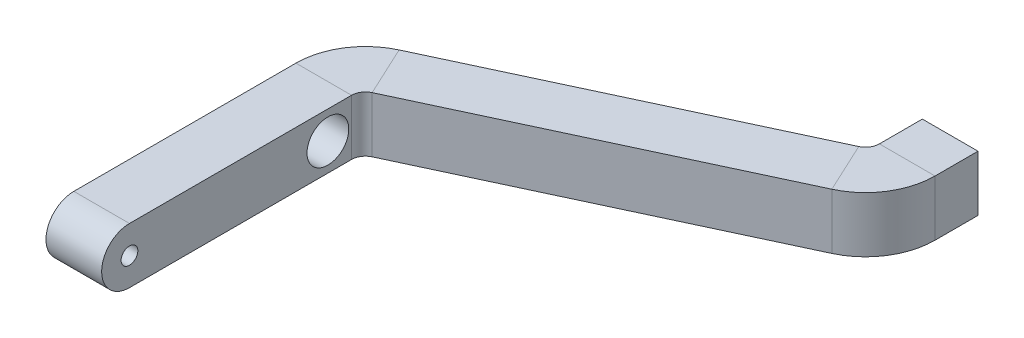
SolidWorks part; units mm, degrees
ref_plane "前视基准面" through (0, 0, 0) normal (0, 0, 1) x (1, 0, 0)
ref_plane "上视基准面" through (0, 0, 0) normal (0, 1, 0) x (1, 0, 0)
ref_plane "右视基准面" through (0, 0, 0) normal (1, 0, 0) x (0, 0, -1)
sketch "草图1" plane through (0, 0, 0) normal (0, 1, 0) x (1, 0, 0)
  line L0 (0, 0) -> (0, -30.8879)
  line L1 (-17.3215, -58.0771) -> (-242.6785, -163.1629)
  line L2 (-260, -190.3521) -> (-260, -370)
  arc A0 (-242.6785, -163.1629) -> (-260, -190.3521) centre (-230, -190.3521) ccw
  arc A1 (0, -30.8879) -> (-17.3215, -58.0771) centre (-30, -30.8879) cw
  point P9 (0, -50)
  dimension "D5" = 30
  dimension "D1" = 260
  dimension "D2" = 115
  dimension "D3" = 370
  dimension "D4" = 50
sketch "草图2" plane through (0, 0, 0) normal (0, 0, 1) x (1, 0, 0)
  line L1 (-20, 20) -> (20, 20)
  line L2 (-20, 20) -> (-20, -20)
  line L3 (-20, -20) -> (20, -20)
  line L4 (20, 20) -> (20, -20)
  line L5 (-20, 20) -> (20, -20) construction
  line L6 (-20, -20) -> (20, 20) construction
  point P0 (0, 0)
  dimension "D1" = 40
  dimension "D2" = 40
sweep "扫描1" add profiles "草图2" path "草图1"
fillet "圆角1" 2 edges at (-260, 20, 370) (-260, -20, 370) type full round first side face at (-260, 20, 280.176) second side face at (-260, -20, 280.176) middle face at (-260, 0, 370)
sketch "草图3" plane through (-280, 0, 0) normal (-1, 0, 0) x (0, 0, 1)
  circle A0 centre (350, 0) radius 6
  dimension "D1" = 12
extrude "切除-拉伸1" cut sketch "草图3" against normal through all
sketch "草图4" plane through (0, 0, 0) normal (0, 0, -1) x (-1, 0, 0)
  circle A0 centre (0, 0) radius 10
  dimension "D1" = 20
extrude "切除-拉伸2" cut sketch "草图4" against normal blind 10
sketch "草图5" plane through (-280, 0, 0) normal (-1, 0, 0) x (0, 0, 1)
  line L0 (190.3521, 20) -> (190.3521, -20) construction
  circle A0 centre (207.3521, 0) radius 15
  dimension "D1" = 30
  dimension "D2" = 17
extrude "切除-拉伸3" cut sketch "草图5" against normal through all
